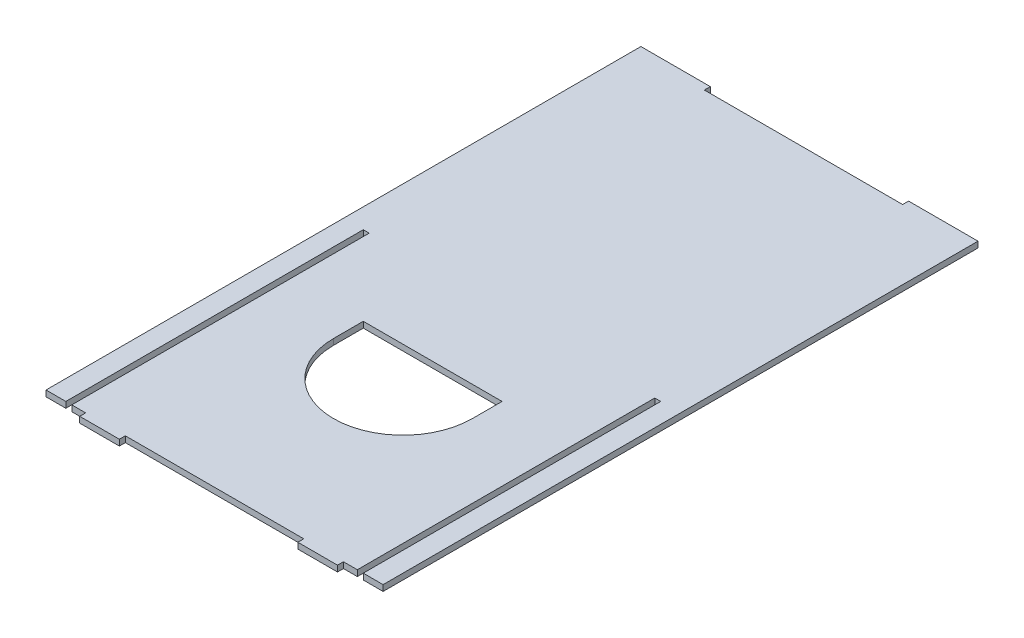
SolidWorks part; units mm, degrees
ref_plane "Front Plane" through (0, 0, 0) normal (0, 0, 1) x (1, 0, 0)
ref_plane "Top Plane" through (0, 0, 0) normal (0, 1, 0) x (1, 0, 0)
ref_plane "Right Plane" through (0, 0, 0) normal (1, 0, 0) x (0, 0, -1)
sketch "Sketch1" plane through (0, 0, 0) normal (0, 1, 0) x (1, 0, 0)
  line L0 (300, 0) -> (300, -6)
  line L2 (0, 0) -> (0, 600)
  line L3 (0, 600) -> (340, 600)
  line L4 (340, 0) -> (340, 600)
  line L5 (300, -6) -> (260, -6)
  line L6 (260, -6) -> (260, 0)
  line L7 (40, 0) -> (40, -6)
  line L8 (40, -6) -> (80, -6)
  line L9 (80, -6) -> (80, 0)
  line L10 (40, 0) -> (0, 0)
  line L11 (80, 0) -> (260, 0)
  line L12 (300, 0) -> (340, 0)
  point P11 (80, -3)
  dimension "D1" = 340
  dimension "D2" = 600
  dimension "D3" = 40
  dimension "D4" = 6
  dimension "D5" = 40
  dimension "D6" = 180
extrude "Boss-Extrude1" add sketch "Sketch1" along normal blind 6
sketch "Sketch2" plane through (0, 6, 0) normal (0, 1, 0) x (1, 0, 0)
  line L1 (20, 0) -> (26, 0)
  line L2 (20, 0) -> (20, 300)
  line L3 (20, 300) -> (26, 300)
  line L4 (26, 0) -> (26, 300)
  line L5 (0, 600) -> (0, 0) construction
  line L6 (0, 0) -> (40, 0) construction
  line L7 (0, 0) -> (40, 0) construction
  dimension "D1" = 300
  dimension "D2" = 6
  dimension "D3" = 20
extrude "Cut-Extrude1" cut sketch "Sketch2" against normal blind 6
pattern_linear "LPattern1" count 2 spacing 294 along (1, 0, 0) of "Cut-Extrude1"
sketch "Sketch3" plane through (0, 6, 0) normal (0, 1, 0) x (1, 0, 0)
  line L0 (100, 190) -> (100, 220)
  line L3 (340, 600) -> (0, 600) construction
  line L4 (70, 600) -> (270, 600)
  line L5 (70, 600) -> (70, 594)
  line L6 (70, 594) -> (270, 594)
  line L7 (270, 600) -> (270, 594)
  line L9 (240, 190) -> (240, 220)
  line L10 (100, 220) -> (240, 220)
  line L12 (0, 600) -> (0, 0) construction
  line L13 (80, 0) -> (260, 0) construction
  arc A1 (100, 190) -> (240, 190) centre (170, 190) ccw
  point P14 (170, 600)
  dimension "D1" = 200
  dimension "D2" = 70
  dimension "D3" = 190
  dimension "D4" = 170
  dimension "D6" = 140
  dimension "D5" = 6
  dimension "D8" = 30
extrude "Cut-Extrude2" cut sketch "Sketch3" against normal blind 6
